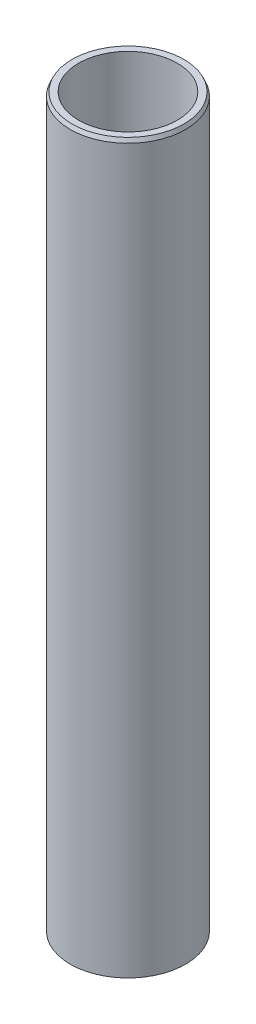
SolidWorks part; units mm, degrees
ref_plane "Front Plane" through (0, 0, 0) normal (0, 0, 1) x (1, 0, 0)
ref_plane "Top Plane" through (0, 0, 0) normal (0, 1, 0) x (1, 0, 0)
ref_plane "Right Plane" through (0, 0, 0) normal (1, 0, 0) x (0, 0, -1)
sketch "Sketch1" plane through (0, 0, 0) normal (0, 1, 0) x (1, 0, 0)
  circle A0 centre (0, 0) radius 47.5
  dimension "SHAFT_OD" = 95
extrude "Boss-Extrude1" add sketch "Sketch1" along normal blind 600
sketch "Sketch2" plane through (0, 0, 0) normal (0, 1, 0) x (1, 0, 0)
  circle A0 centre (0, 0) radius 40.6858
  dimension "BORE_D" = 81.3717
extrude "Cut-Extrude1" cut sketch "Sketch2" along normal through all
chamfer "Chamfer1" distance 3.2389 angle 23.717 2 edges at (0, 600, 47.5) (0, 0, 47.5) first distance on face at (0, 600, 47.5) first distance on face at (0, 0, 40.6858)
